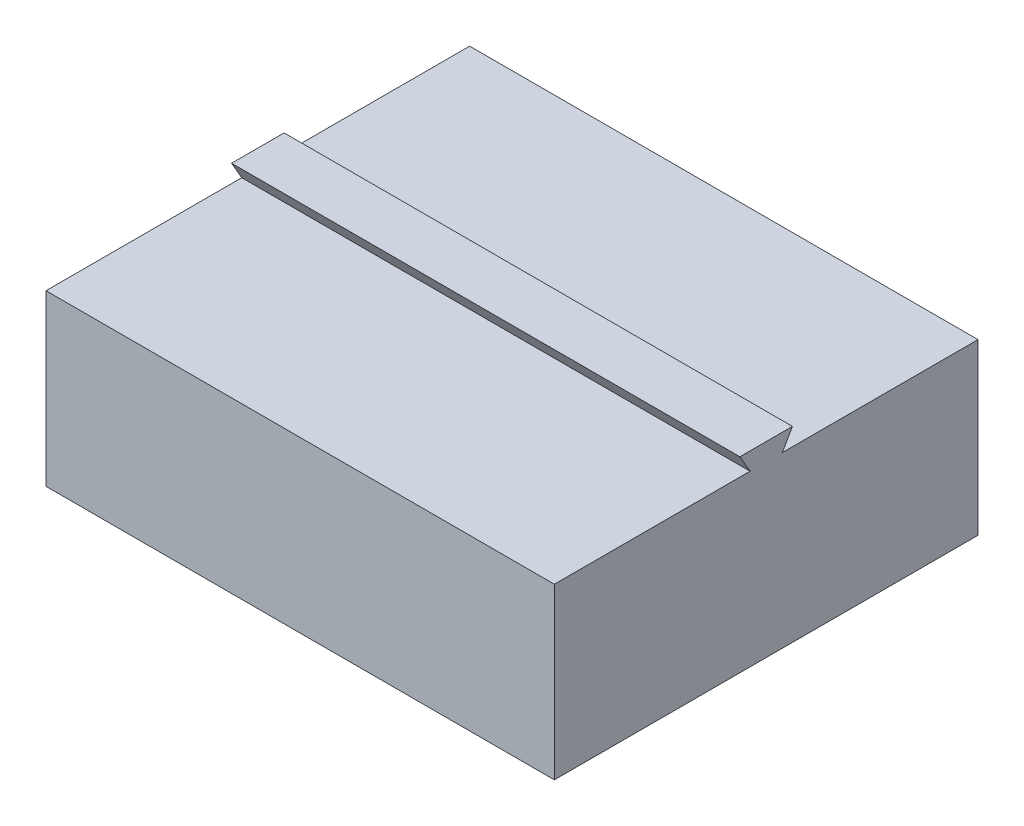
SolidWorks part; units mm, degrees
ref_plane "Front Plane" through (0, 0, 0) normal (0, 0, 1) x (1, 0, 0)
ref_plane "Top Plane" through (0, 0, 0) normal (0, 1, 0) x (1, 0, 0)
ref_plane "Right Plane" through (0, 0, 0) normal (1, 0, 0) x (0, 0, -1)
sketch "Sketch1" plane through (0, 0, 0) normal (0, 1, 0) x (1, 0, 0)
  line L1 (60, -50) -> (-60, -50)
  line L2 (60, -50) -> (60, 50)
  line L3 (60, 50) -> (-60, 50)
  line L4 (-60, -50) -> (-60, 50)
  line L5 (60, -50) -> (-60, 50) construction
  line L6 (60, 50) -> (-60, -50) construction
  point P0 (0, 0)
  dimension "D1" = 120
  dimension "D2" = 100
extrude "Boss-Extrude1" add sketch "Sketch1" along normal blind 40
sketch "Sketch2" plane through (60, 0, 0) normal (1, 0, 0) x (0, 0, -1)
  line L0 (-3.8, 40) -> (-6.2018, 44.16)
  line L1 (-50, 40) -> (50, 40) construction
  line L2 (-6.2018, 44.16) -> (6.2018, 44.16)
  line L3 (6.2018, 44.16) -> (3.8, 40)
  line L4 (3.8, 40) -> (-3.8, 40)
  line L5 (0, -1000) -> (0, 49000) construction
  dimension "D1" = 60
  dimension "D2" = 4.16
  dimension "D3" = 60
  dimension "D4" = 7.6
extrude "Boss-Extrude2" add sketch "Sketch2" against normal up to surface (120 mm away) up to face at (-60, 20, 0)
ref_point "Point1"
ref_axis "Axis1" through (0, 0, 0) along (0, 1, 0)
ref_point "Point2"
ref_axis "Axis2" through (-60, 20.229, 0) along (1, 0, 0)
ref_point "CM"
